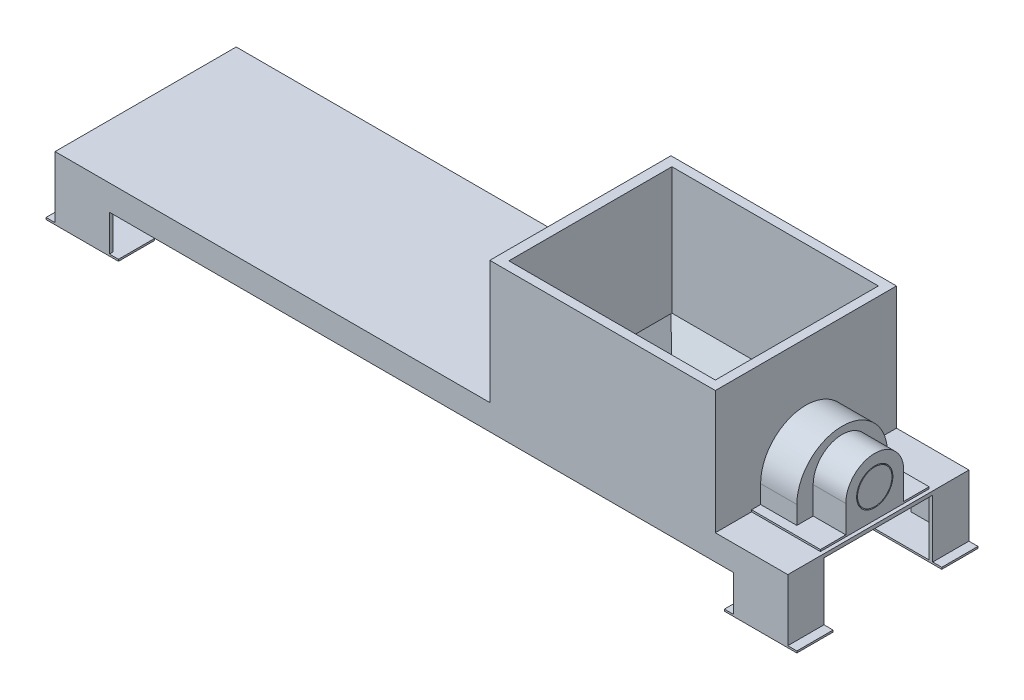
SolidWorks part; units mm, degrees
ref_plane "Front Plane" through (0, 0, 0) normal (0, 0, 1) x (1, 0, 0)
ref_plane "Top Plane" through (0, 0, 0) normal (0, 1, 0) x (1, 0, 0)
ref_plane "Right Plane" through (0, 0, 0) normal (1, 0, 0) x (0, 0, -1)
sketch "Sketch1" plane through (0, 0, 0) normal (0, 1, 0) x (1, 0, 0)
  line L1 (0, 0) -> (4045, 0)
  line L2 (0, 0) -> (0, 1000)
  line L3 (0, 1000) -> (4045, 1000)
  line L4 (4045, 0) -> (4045, 1000)
  dimension "D1" = 4045
  dimension "D2" = 1000
extrude "Boss-Extrude1" add sketch "Sketch1" along normal blind 340
sketch "Sketch2" plane through (0, 0, 0) normal (0, -1, 0) x (1, 0, 0)
  line L0 (0, 0) -> (4045, 0) construction
  line L1 (0, -200) -> (4045, -200)
  line L2 (0, -200) -> (0, -800)
  line L3 (0, -800) -> (4045, -800)
  line L4 (4045, -200) -> (4045, -800)
  line L5 (4045, -1000) -> (0, -1000) construction
  line L6 (4045, 0) -> (4045, -1000) construction
  line L7 (0, -1000) -> (0, 0) construction
  dimension "D1" = 200
  dimension "D2" = 200
  dimension "D3" = 0
  dimension "D4" = 0
extrude "Cut-Extrude1" cut sketch "Sketch2" against normal blind 320
sketch "Sketch3" plane through (0, 0, 0) normal (0, -1, 0) x (1, 0, 0)
  line L0 (4045, -200) -> (0, -200) construction
  line L1 (300, 0) -> (3745, 0)
  line L2 (300, 0) -> (300, -200)
  line L3 (300, -200) -> (3745, -200)
  line L4 (3745, 0) -> (3745, -200)
  line L5 (0, 0) -> (4045, 0) construction
  line L6 (0, -200) -> (0, 0) construction
  line L7 (4045, 0) -> (4045, -200) construction
  line L8 (300, -800) -> (300, -1000)
  line L9 (300, -800) -> (3745, -800)
  line L10 (3745, -800) -> (3745, -1000)
  line L11 (300, -1000) -> (3745, -1000)
  dimension "D1" = 0
  dimension "D2" = 0
  dimension "D3" = 300
  dimension "D4" = 300
  dimension "D5" = 2
extrude "Cut-Extrude2" cut sketch "Sketch3" against normal blind 200
sketch "Sketch4" plane through (0, 0, 0) normal (0, -1, 0) x (1, 0, 0)
  line L0 (4045, -200) -> (0, -200) construction
  line L1 (-50, 0) -> (350, 0)
  line L2 (-50, 0) -> (-50, -200)
  line L3 (-50, -200) -> (350, -200)
  line L4 (350, 0) -> (350, -200)
  line L5 (0, 0) -> (300, 0) construction
  line L6 (0, -200) -> (0, 0) construction
  line L7 (300, 0) -> (300, -200) construction
  line L8 (3695, 0) -> (3695, -200)
  line L9 (3695, 0) -> (4095, 0)
  line L10 (4095, 0) -> (4095, -200)
  line L11 (3695, -200) -> (4095, -200)
  line L12 (3695, -800) -> (3695, -1000)
  line L13 (3695, -800) -> (4095, -800)
  line L14 (4095, -800) -> (4095, -1000)
  line L15 (3695, -1000) -> (4095, -1000)
  line L16 (-50, -800) -> (-50, -1000)
  line L17 (-50, -800) -> (350, -800)
  line L18 (350, -800) -> (350, -1000)
  line L19 (-50, -1000) -> (350, -1000)
  dimension "D1" = 0
  dimension "D2" = 0
  dimension "D3" = 50
  dimension "D4" = 50
  dimension "D5" = 2
  dimension "D6" = 2
extrude "Boss-Extrude2" add sketch "Sketch4" along normal blind 10
sketch "Sketch5" plane through (0, 340, 0) normal (0, 1, 0) x (1, 0, 0)
  line L0 (0, 0) -> (4045, 0) construction
  line L1 (2400, 1000) -> (3645, 1000)
  line L2 (2400, 1000) -> (2400, 0)
  line L3 (2400, 0) -> (3645, 0)
  line L4 (3645, 1000) -> (3645, 0)
  line L6 (4045, 1000) -> (0, 1000) construction
  line L7 (4045, 0) -> (4045, 1000) construction
  line L8 (0, 1000) -> (0, 0) construction
  dimension "D1" = 0
  dimension "D2" = 0
  dimension "D3" = 400
  dimension "D4" = 2400
extrude "Boss-Extrude3" add sketch "Sketch5" along normal blind 680
sketch "Sketch6" plane through (0, -10, 0) normal (0, -1, 0) x (1, 0, 0)
  line L0 (3745, 0) -> (300, 0) construction
  line L1 (20, -20) -> (4025, -20)
  line L2 (20, -20) -> (20, -980)
  line L3 (20, -980) -> (4025, -980)
  line L4 (4025, -20) -> (4025, -980)
  line L5 (-50, -800) -> (-50, -1000) construction
  line L6 (300, -1000) -> (3745, -1000) construction
  line L7 (4095, -200) -> (4095, 0) construction
  dimension "D1" = 20
  dimension "D2" = 70
  dimension "D3" = 20
  dimension "D4" = 70
extrude "Cut-Extrude3" cut sketch "Sketch6" against normal blind 320 from offset 10 offset against normal yes
sketch "Sketch7" plane through (0, 320, 0) normal (0, -1, 0) x (1, 0, 0)
  line L1 (2455, -50) -> (3595, -50)
  line L2 (2455, -50) -> (2455, -950)
  line L3 (2455, -950) -> (3595, -950)
  line L4 (3595, -50) -> (3595, -950)
  line L5 (4045, -800) -> (4045, -200) construction
  line L6 (3745, 0) -> (300, 0) construction
  line L7 (2435, -30) -> (3615, -30)
  line L8 (3615, -30) -> (3615, -970)
  line L9 (2435, -970) -> (3615, -970)
  line L10 (2435, -30) -> (2435, -970)
  dimension "D1" = 1140
  dimension "D2" = 900
  dimension "D3" = 450
  dimension "D4" = 50
  dimension "D5" = 20
extrude "Cut-Extrude5" cut sketch "Sketch7" against normal through all contours L4 L3 L2 L1
extrude "Boss-Extrude4" add sketch "Sketch7<3>" along normal blind 180 contours L8 L9 L10 L7
sketch "Sketch7<3>" plane through (0, 320, 0) normal (0, -1, 0) x (1, 0, 0) same geometry as "Sketch7"
draft "Draft3" type of draft neutral plane draft angle 30 faces to draft 4 face at (3025, 230, -30) face at (3615, 230, -500) face at (3025, 230, -970) face at (2435, 230, -500) neutral plane through (0, 320, 0) neutral plane normal (0, 1, 0) reverse direction yes parameters "D1"=30
sketch "Sketch8" plane through (0, 320, 0) normal (0, 1, 0) x (1, 0, 0)
  line L0 (2455, 950) -> (3595, 950) construction
  line L1 (3595, 50) -> (2450, 50)
  line L2 (3595, 50) -> (3595, 950)
  line L3 (3595, 950) -> (2450, 950)
  line L4 (2450, 50) -> (2450, 950)
sketch "Sketch10" plane through (0, 140, 0) normal (0, -1, 0) x (1, 0, 0)
  line L0 (2538.923, -133.923) -> (3511.077, -133.923) construction
  line L1 (2558.923, -153.923) -> (3491.077, -153.923)
  line L2 (2558.923, -153.923) -> (2558.923, -846.077)
  line L3 (2558.923, -846.077) -> (3491.077, -846.077)
  line L4 (3491.077, -153.923) -> (3491.077, -846.077)
  line L5 (3511.077, -133.923) -> (3511.077, -866.077) construction
  line L6 (2538.923, -866.077) -> (3511.077, -866.077) construction
  line L7 (2538.923, -133.923) -> (2538.923, -866.077) construction
  dimension "D1" = 20
  dimension "D2" = 20
  dimension "D3" = 20
  dimension "D4" = 20
loft "Cut-Loft2" cut profiles "Sketch8", "Sketch10" connector at (2450, 320, -50) connector at (2558.923, 140, -153.923)
ref_plane "Plane1" through (3845, 0, 0) normal (1, 0, 0) x (0, 0, -1)
sketch "Sketch12" plane through (3845, 0, 0) normal (1, 0, 0) x (0, 0, -1)
  line L0 (0, 340) -> (1000, 340) construction
  line L2 (250, 450) -> (250, 350)
  line L3 (250, 350) -> (750, 350)
  line L4 (750, 450) -> (750, 350)
  line L5 (1000, 1020) -> (1000, 340) construction
  arc A0 (750, 450) -> (250, 450) centre (500, 450) ccw
  dimension "D1" = 500
  dimension "D2" = 10
  dimension "D3" = 250
  dimension "D4" = 100
extrude "Boss-Extrude5" add sketch "Sketch12" against normal up to next
sketch "Sketch13" plane through (3845, 0, 0) normal (1, 0, 0) x (0, 0, -1)
  line L1 (0, 340) -> (1000, 340) construction
  line L3 (340, 500) -> (340, 340)
  line L4 (340, 340) -> (660, 340)
  line L5 (660, 500) -> (660, 340)
  circle A0 centre (500, 500) radius 100
  arc A1 (750, 450) -> (250, 450) centre (500, 450) ccw construction
  arc A2 (660, 500) -> (340, 500) centre (500, 500) ccw
  point P5 (201.3033, 672.2588)
  dimension "D2" = 200
  dimension "D4" = 60
  dimension "D1" = 0
  dimension "D5" = 0
  dimension "D6" = 320
  dimension "D7" = 160
  dimension "D8" = 160
extrude "Boss-Extrude6" add sketch "Sketch13" along normal blind 180
sketch "Sketch14" plane through (0, 340, 0) normal (0, 1, 0) x (1, 0, 0)
  line L0 (3645, 0) -> (3645, 1000) construction
  line L1 (3645, 200) -> (4025, 200)
  line L2 (3645, 200) -> (3645, 800)
  line L3 (3645, 800) -> (4025, 800)
  line L4 (4025, 200) -> (4025, 800)
  line L5 (4045, 1000) -> (3645, 1000) construction
  dimension "D1" = 600
  dimension "D2" = 380
  dimension "D3" = 0
  dimension "D4" = 200
extrude "Boss-Extrude7" add sketch "Sketch14" along normal blind 10
sketch "Sketch15" plane through (3845, 0, 0) normal (1, 0, 0) x (0, 0, -1)
  circle A0 centre (500, 500) radius 95
  dimension "D1" = 190
extrude "Boss-Extrude8" add sketch "Sketch15" along normal up to surface (180 mm away) up to face at (4025, 405, -500)
